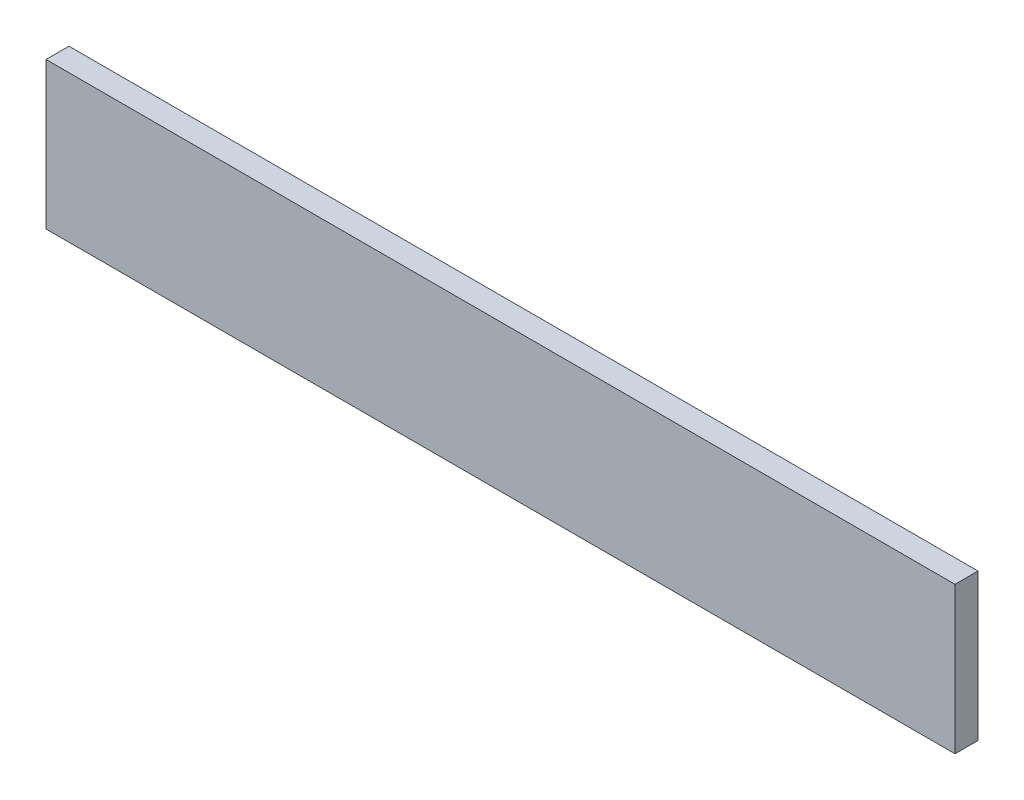
SolidWorks part; units mm, degrees
ref_plane "Alzado" through (0, 0, 0) normal (0, 0, 1) x (1, 0, 0)
ref_plane "Planta" through (0, 0, 0) normal (0, 1, 0) x (1, 0, 0)
ref_plane "Vista lateral" through (0, 0, 0) normal (1, 0, 0) x (0, 0, -1)
sketch "Croquis1" plane through (0, 0, 0) normal (0, 0, 1) x (1, 0, 0)
  line L1 (-356.075, -57.5) -> (356.075, -57.5)
  line L2 (-356.075, -57.5) -> (-356.075, 57.5)
  line L3 (-356.075, 57.5) -> (356.075, 57.5)
  line L4 (356.075, -57.5) -> (356.075, 57.5)
  line L5 (-356.075, -57.5) -> (356.075, 57.5) construction
  line L6 (-356.075, 57.5) -> (356.075, -57.5) construction
  point P0 (0, 0)
  dimension "D1" = 115
  dimension "D2" = 712.15
extrude "Saliente-Extruir1" add sketch "Croquis1" along normal blind 18
